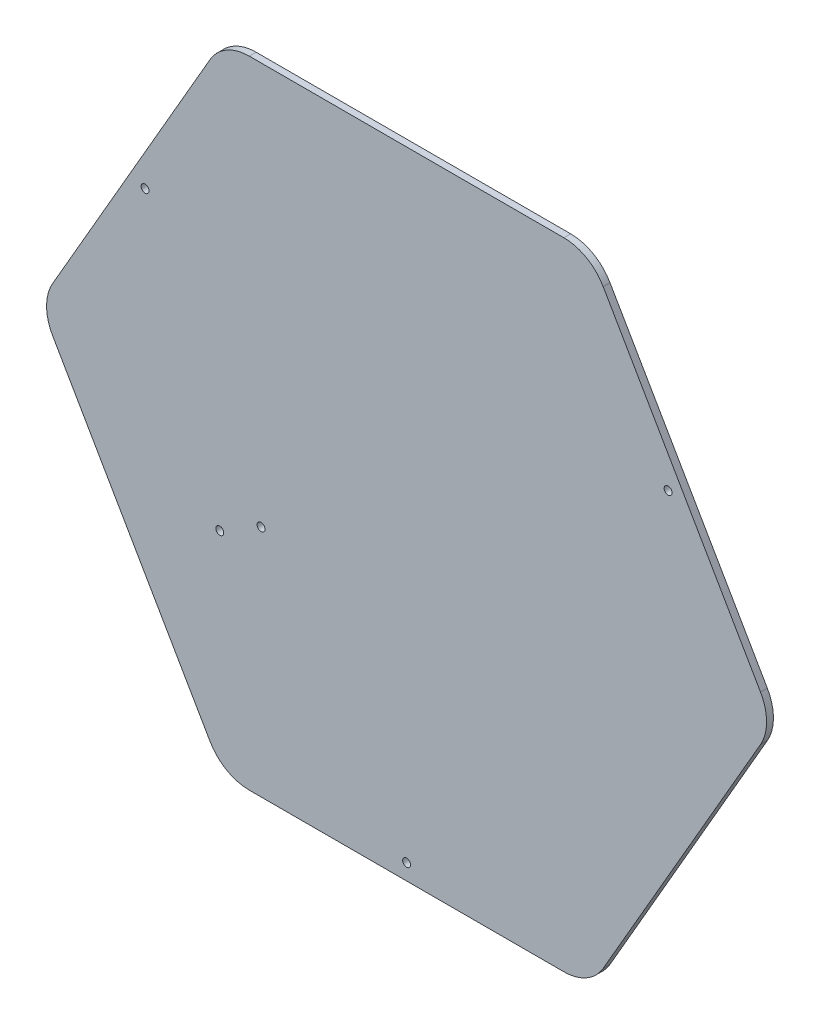
SolidWorks part; units mm, degrees
ref_plane "Alzado" through (0, 0, 0) normal (0, 0, 1) x (1, 0, 0)
ref_plane "Planta" through (0, 0, 0) normal (0, 1, 0) x (1, 0, 0)
ref_plane "Vista lateral" through (0, 0, 0) normal (1, 0, 0) x (0, 0, -1)
sketch "Croquis1" plane through (0, 0, 0) normal (0, 0, 1) x (1, 0, 0)
  line L0 (11.25, 96) -> (-11.25, 84) construction
  line L1 (-11.25, 96) -> (11.25, 96)
  line L2 (-11.25, 96) -> (-11.25, 84)
  line L3 (-11.25, 84) -> (11.25, 84)
  line L4 (11.25, 96) -> (11.25, 84)
  line L5 (-11.25, 96) -> (11.25, 84) construction
  line L6 (88.7634, -38.2572) -> (78.3711, -32.2572)
  line L7 (88.7634, -38.2572) -> (77.5134, -57.7428)
  line L8 (77.5134, -57.7428) -> (67.1211, -51.7428)
  line L9 (78.3711, -32.2572) -> (67.1211, -51.7428)
  line L10 (-77.5134, -57.7428) -> (-67.1211, -51.7428)
  line L11 (-77.5134, -57.7428) -> (-88.7634, -38.2572)
  line L12 (-88.7634, -38.2572) -> (-78.3711, -32.2572)
  line L13 (-67.1211, -51.7428) -> (-78.3711, -32.2572)
  line L14 (0, -0.7536) -> (0, 0) construction
  line L15 (0, 0) -> (0, 17.5) construction
  line L17 (-80.829, -140) -> (80.829, -140)
  line L18 (80.829, -140) -> (161.6581, 0)
  line L19 (161.6581, 0) -> (80.829, 140)
  line L20 (80.829, 140) -> (-80.829, 140)
  line L21 (-80.829, 140) -> (-161.6581, 0)
  line L22 (-161.6581, 0) -> (-80.829, -140)
  circle A0 centre (0, 0) radius 150
  circle A1 centre (0, 0) radius 10.8
  circle A2 centre (0, 0) radius 90 construction
  circle A3 centre (0, 90) radius 40 construction
  circle A4 centre (77.9423, -45) radius 40 construction
  circle A5 centre (-77.9423, -45) radius 40 construction
  circle A6 centre (0, 0) radius 17.5 construction
  circle A7 centre (0, 17.5) radius 2.6
  circle A8 centre (0, 0) radius 140 construction
  circle A9 centre (15.1554, -8.75) radius 2.6
  circle A10 centre (-15.1554, -8.75) radius 2.6
  point P11 (0, 90)
  point P18 (0, 0)
  point P28 (0, 0)
  point P39 (0, 0)
  dimension "D1" = 300
  dimension "D2" = 21.6
  dimension "D3" = 180
  dimension "D4" = 80
  dimension "D9" = 5.2
  dimension "D10" = 3
  dimension "D11" = 50
  dimension "D5" = 12
  dimension "D6" = 22.5
  dimension "D7" = 3
  dimension "D8" = 3
extrude "Saliente-Extruir1" add sketch "Croquis1" along normal blind 3 contours L19 A0 L20 L21 L22 L17 L18 A10 A9 A7 A1 L1 L4 L3 L2 L9 L6 L7 L8 L13 L10 L11 L12 | A0 L20 L21 | A0 L19 L20 | A0 L18 L19 | A0 L17 L18 | A0 L22 L17 | A0 L21 L22 | A10 | A1 | A9 | A7 | L11 L12 L13 L10 | L9 L8 L7 L6 | L3 L4 L1 L2 region at (-76.7492, -132.9335, 0) region at (-72.9482, -126.3499, 0) region at (76.7492, -132.9335, 0) region at (-153.4984, 0, 0) region at (153.4984, 0, 0) region at (-76.7492, 132.9335, 0) region at (76.7492, 132.9335, 0) region at (0, 0, 0) region at (0, 17.5, 0) region at (15.1554, -8.75, 0) region at (-15.1554, -8.75, 0)
fillet "Redondeo1" radius 20 6 edges at (80.829, 140, 1.5) (-80.829, 140, 1.5) (-161.6581, 0, 1.5) (-80.829, -140, 1.5) (80.829, -140, 1.5) (161.6581, 0, 1.5)
sketch "Croquis2" plane through (0, 0, 0) normal (0, 0, -1) x (1, 0, 0)
  circle A0 centre (0, 133) radius 1.75
  circle A1 centre (115.1814, -66.5) radius 1.75
  circle A2 centre (-115.1814, -66.5) radius 1.75
  point P9 (0, 0)
  dimension "D1" = 3
extrude "Cortar-Extruir1" cut sketch "Croquis2" against normal through all
sketch "Croquis3" plane through (0, 0, 86.15) normal (0, 0, 1) x (1, 0, 0)
  circle A0 centre (-64.0939, -37.0046) radius 1.75
  circle A1 centre (-82.2805, -47.5046) radius 1.75
  dimension "D1" = 3.5
extrude "Cortar-Extruir2" cut sketch "Croquis3" against normal through all
